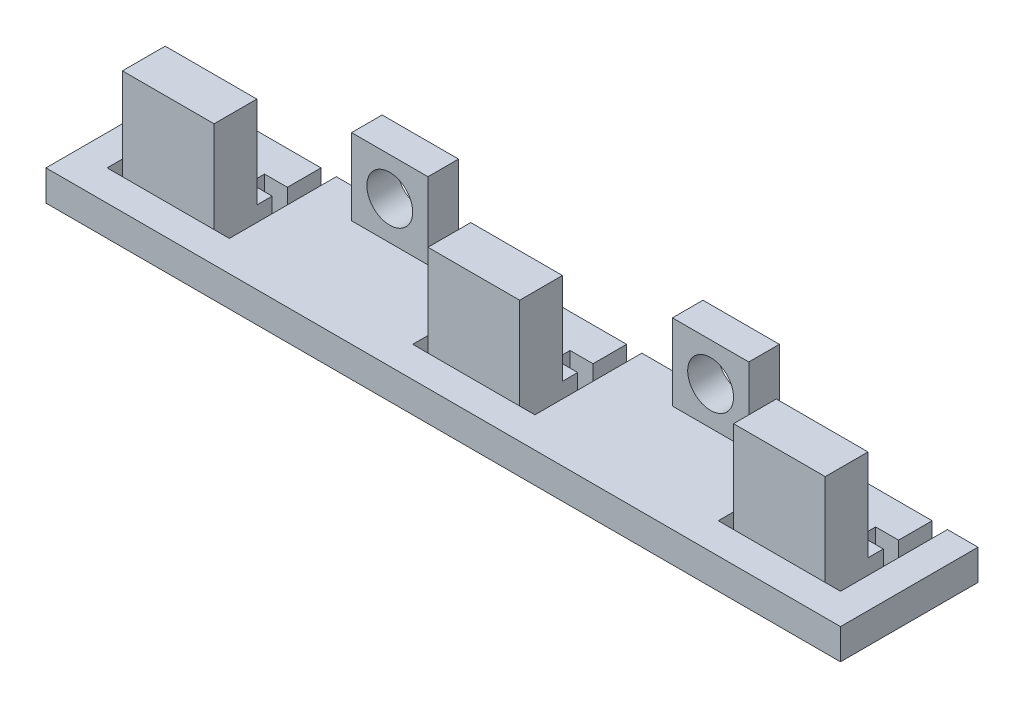
SolidWorks part; units mm, degrees
ref_plane "前视基准面" through (0, 0, 0) normal (0, 0, 1) x (1, 0, 0)
ref_plane "上视基准面" through (0, 0, 0) normal (0, 1, 0) x (1, 0, 0)
ref_plane "右视基准面" through (0, 0, 0) normal (1, 0, 0) x (0, 0, -1)
other "Configuration Table"
sketch "草图1" plane through (0, 0, 0) normal (0, 1, 0) x (1, 0, 0)
  line L1 (0, 0) -> (52, 0)
  line L2 (0, 0) -> (0, -9)
  line L3 (0, -9) -> (52, -9)
  line L4 (52, 0) -> (52, -9)
  line L9 (10, 0) -> (9, 0)
  line L70 (10, 0) -> (10, -7)
  line L71 (10, -7) -> (9, -7)
  line L72 (9, 0) -> (9, -7)
  line L73 (2, 0) -> (3, 0)
  line L74 (2, 0) -> (2, -7)
  line L75 (2, -7) -> (3, -7)
  line L76 (3, 0) -> (3, -7)
  line L81 (3, -2.2) -> (4.5, -2.2)
  line L82 (3, -2.2) -> (3, -3.2)
  line L83 (3, -3.2) -> (4.5, -3.2)
  line L84 (4.5, -2.2) -> (4.5, -3.2)
  line L85 (9, -2.2) -> (7.5, -2.2)
  line L86 (9, -2.2) -> (9, -3.2)
  line L87 (9, -3.2) -> (7.5, -3.2)
  line L88 (7.5, -2.2) -> (7.5, -3.2)
  line L89 (3, -7) -> (9, -7)
  line L90 (3, -7) -> (3, -4.2)
  line L91 (3, -4.2) -> (9, -4.2)
  line L92 (9, -7) -> (9, -4.2)
  line L93 (13, 0) -> (18, 0)
  line L94 (13, 0) -> (13, -2)
  line L95 (13, -2) -> (18, -2)
  line L96 (18, 0) -> (18, -2)
  line L97 (34, 0) -> (39, 0)
  line L98 (34, 0) -> (34, -2)
  line L99 (34, -2) -> (39, -2)
  line L100 (39, 0) -> (39, -2)
  dimension "D1" = 52
  dimension "D2" = 1
  dimension "D3" = 1
  dimension "D4" = 1.5
  dimension "D5" = 2
  dimension "D6" = 7
  dimension "D7" = 2
  dimension "D8" = 6
  dimension "D9" = 2.2
  dimension "D10" = 2.8
  dimension "D11" = 5
  dimension "D12" = 2
  dimension "D13" = 13
  dimension "D14" = 13
extrude "凸台-拉伸1" add sketch "草图1" along normal blind 2 contours L3 L4 L1 L2
extrude "切除-拉伸2" cut sketch "草图1<5>" along normal through all contours L70 L71 L72 L9 | L85 L88 L87 L86 | L81 L84 L83 L82 | L76 L75 L74 L73
sketch "草图1<5>" plane through (0, 0, 0) normal (0, 1, 0) x (1, 0, 0) same geometry as "草图1"
extrude "凸台-拉伸2" add sketch "草图1<6>" along normal blind 6 from surface contours L91 L76 L89 L72 region at (6, 0, 5.6) starting at face at (10, 2, 3.38)
sketch "草图1<6>" plane through (0, 0, 0) normal (0, 1, 0) x (1, 0, 0) same geometry as "草图1"
pattern_linear "阵列(线性)1" count 3 spacing 20 along (1, 0, 0) of "切除-拉伸2", "凸台-拉伸2"
extrude "凸台-拉伸3" add sketch "草图1<7>" along normal blind 5 from surface contours L95 L96 L93 L94 | L99 L100 L97 L98 starting at face at (26, 2, 4.6364)
sketch "草图1<7>" plane through (0, 0, 0) normal (0, 1, 0) x (1, 0, 0) same geometry as "草图1"
sketch "草图2" plane through (0, 0, 2) normal (0, 0, 1) x (1, 0, 0)
  line L1 (18, 7) -> (13, 7) construction
  line L2 (18, 7) -> (18, 2) construction
  line L3 (39, 7) -> (34, 7) construction
  circle A0 centre (36.5, 4.5) radius 1.5
  circle A1 centre (15.5, 4.5) radius 1.5
  point P8 (15.5, 7)
  point P9 (18, 4.5)
  point P10 (0, 0)
  point P13 (36.5, 7)
  dimension "D1" = 3
extrude "切除-拉伸3" cut sketch "草图2" against normal through all
